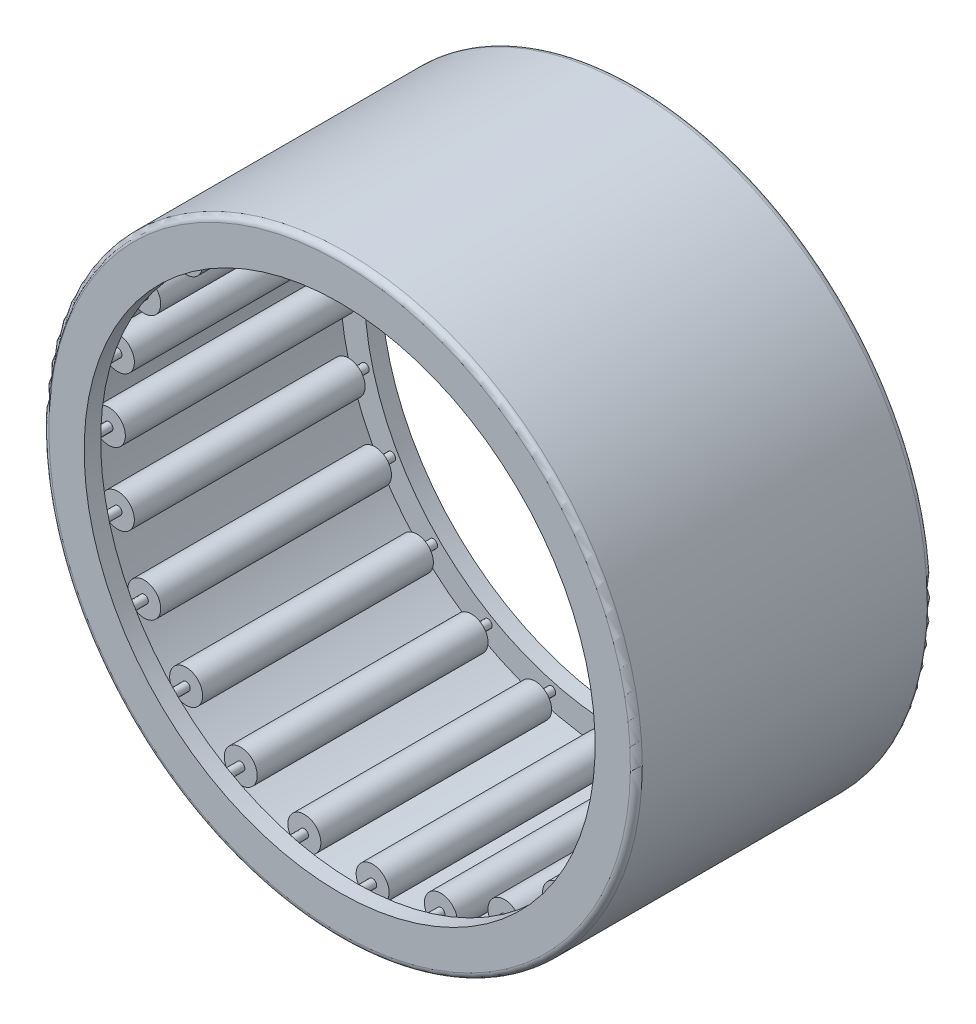
SolidWorks part; units mm, degrees
ref_plane "Front Plane" through (0, 0, 0) normal (0, 0, 1) x (1, 0, 0)
ref_plane "Top Plane" through (0, 0, 0) normal (0, 1, 0) x (1, 0, 0)
ref_plane "Right Plane" through (0, 0, 0) normal (1, 0, 0) x (0, 0, -1)
sketch "Sketch1" plane through (0, 0, 0) normal (1, 0, 0) x (0, 0, -1)
  line L0 (-9.525, 0) -> (9.525, 0) construction
  line L1 (0, 0) -> (0, 19.05) construction
  line L2 (-9.525, 0) -> (-9.525, 19.05) construction
  line L3 (-9.525, 19.05) -> (9.525, 19.05)
  line L4 (9.525, 19.05) -> (9.525, 0) construction
  line L5 (9.525, 0) -> (8.4667, 0) construction
  line L6 (8.4667, 0) -> (8.4667, 17.9917) construction
  line L7 (8.4667, 17.9917) -> (-8.4667, 17.9917)
  line L8 (-8.4667, 17.9917) -> (-8.4667, 0) construction
  line L9 (-8.4667, 0) -> (-9.525, 0) construction
  line L10 (-9.525, 19.05) -> (-9.525, 16.4042)
  line L11 (-9.525, 16.4042) -> (-8.4667, 16.4042)
  line L12 (-8.4667, 16.4042) -> (-8.4667, 17.9917)
  line L13 (8.4667, 19.05) -> (8.4667, 17.9917) construction
  line L14 (8.4667, 17.9917) -> (8.4667, 16.4042)
  line L15 (8.4667, 16.4042) -> (9.525, 16.4042)
  line L16 (9.525, 16.4042) -> (9.525, 19.05)
  line L17 (8.4667, 17.9917) -> (8.4667, 16.9333) construction
  line L18 (8.4667, 16.9333) -> (8.4667, 15.875) construction
  line L19 (8.4667, -17.9917) -> (8.4667, -16.9333) construction
  line L20 (8.4667, -19.05) -> (8.4667, -17.9917) construction
  line L21 (9.525, -16.4042) -> (9.525, -19.05) construction
  line L22 (8.4667, -16.4042) -> (9.525, -16.4042) construction
  line L23 (8.4667, -17.9917) -> (8.4667, -16.4042) construction
  line L24 (-8.4667, -16.4042) -> (-8.4667, -17.9917) construction
  line L25 (-9.525, -16.4042) -> (-8.4667, -16.4042) construction
  line L26 (-9.525, -19.05) -> (-9.525, -16.4042) construction
  line L27 (8.4667, -17.9917) -> (-8.4667, -17.9917) construction
  line L28 (-9.525, -19.05) -> (9.525, -19.05) construction
  point P5 (0, 15.875)
  dimension "Width" = 19.05
  dimension "OD" = 38.1
  dimension "Shaft Dia" = 31.75
revolve "Revolve1" add sketch "Sketch1" angle 360 about L0
sketch "Sketch2" plane through (0, 0, 0) normal (1, 0, 0) x (0, 0, -1)
  line L0 (8.4667, 17.9917) -> (-8.4667, 17.9917) construction
  line L1 (-7.4083, 16.9333) -> (7.4083, 16.9333) construction
  line L2 (-7.4083, 16.9333) -> (-7.4083, 17.9917) construction
  line L3 (-7.4083, 17.9917) -> (7.4083, 17.9917)
  line L4 (7.4083, 16.9333) -> (7.4083, 17.9917) construction
  line L5 (8.4667, 16.4042) -> (9.525, 16.4042) construction
  line L6 (-8.4667, 16.9333) -> (-7.4083, 16.9333) construction
  line L7 (7.4083, 16.9333) -> (8.4667, 16.9333) construction
  line L8 (-9.525, 16.4042) -> (-8.4667, 16.4042) construction
  line L9 (-7.4083, 17.1979) -> (-7.4083, 16.6688) construction
  line L10 (-8.4667, 16.9333) -> (-8.4667, 16.4042) construction
  line L11 (-7.4083, 17.9917) -> (-7.4083, 17.1979)
  line L12 (7.4083, 17.9917) -> (7.4083, 17.1979)
  line L13 (7.4083, 17.1979) -> (-7.4083, 17.1979)
  line L14 (0, 17.9917) -> (0, 15.875) construction
  line L15 (-8.4667, 16.4042) -> (-8.4667, 17.9917) construction
  line L16 (-7.4083, 16.6688) -> (-8.4667, 16.6688) construction
  line L17 (0, 0) -> (9.525, 0) construction
  line L18 (-7.4083, -16.6688) -> (-8.4667, -16.6688) construction
  line L19 (0, -17.9917) -> (0, -15.875) construction
  line L20 (-8.4667, -16.9333) -> (-8.4667, -16.4042) construction
  line L21 (-7.4083, -17.1979) -> (-7.4083, -16.6688) construction
  line L22 (7.4083, -16.9333) -> (8.4667, -16.9333) construction
  line L23 (-8.4667, -16.9333) -> (-7.4083, -16.9333) construction
  line L24 (7.4083, -16.9333) -> (7.4083, -17.9917) construction
  line L25 (-7.4083, -16.9333) -> (-7.4083, -17.9917) construction
  line L26 (-7.4083, -16.9333) -> (7.4083, -16.9333) construction
  line L27 (7.4083, -17.1979) -> (-7.4083, -17.1979) construction
  line L28 (7.4083, -17.9917) -> (7.4083, -17.1979) construction
  line L29 (-7.4083, -17.9917) -> (-7.4083, -17.1979) construction
  line L30 (-7.4083, -17.9917) -> (7.4083, -17.9917) construction
  line L31 (9.525, -19.05) -> (9.525, 19.05) construction
  point P16 (0, 16.9333)
revolve "Revolve2" add sketch "Sketch2" angle 360 about L1
sketch "Sketch3" plane through (0, 0, 0) normal (1, 0, 0) x (0, 0, -1)
  line L0 (8.4667, 17.9917) -> (8.4667, 16.4042) construction
  line L1 (-8.4667, 16.9333) -> (8.4667, 16.9333)
  line L2 (-8.4667, 16.9333) -> (-8.4667, 17.1979)
  line L3 (-8.4667, 17.1979) -> (8.4667, 17.1979)
  line L4 (8.4667, 16.9333) -> (8.4667, 17.1979)
  line L5 (0, 0) -> (9.525, 0) construction
  line L6 (9.525, -19.05) -> (9.525, 19.05) construction
  line L7 (8.4667, -16.9333) -> (8.4667, -17.1979) construction
  line L8 (-8.4667, -17.1979) -> (8.4667, -17.1979) construction
  line L9 (-8.4667, -16.9333) -> (-8.4667, -17.1979) construction
  line L10 (-8.4667, -16.9333) -> (8.4667, -16.9333) construction
revolve "Revolve3" add sketch "Sketch3" angle 360 about L1
ref_axis "Axis1" through (0, 0, -9.525) along (0, 0, 1)
pattern_circular "CirPattern1" count 24 over 360 about axis through (0, 0, -9.525) along (0, 0, 1) of bodies 166 167
fillet "Fillet1" radius 0.381 2 edges at (0, -19.05, -9.525) (0, -19.05, 9.525)
sketch "Sketch4" plane through (0, 0, 0) normal (1, 0, 0) x (0, 0, -1)
  line L1 (9.144, 15.875) -> (7.4083, 15.875)
  line L2 (9.144, 15.875) -> (9.144, 16.4042)
  line L3 (9.144, 16.4042) -> (7.4083, 16.4042)
  line L4 (7.4083, 15.875) -> (7.4083, 16.4042)
  line L5 (-9.525, 16.4042) -> (-8.4667, 16.4042) construction
  line L6 (9.144, -19.05) -> (9.144, 19.05) construction
  line L7 (7.4083, 17.9917) -> (7.4083, 17.1979) construction
revolve "Revolve4" [suppressed] add sketch "Sketch4" angle 360 about L0
sketch "Sketch5" plane through (0, 0, 0) normal (1, 0, 0) x (0, 0, -1)
  line L0 (-9.144, 19.05) -> (-9.144, -19.05) construction
  line L1 (-7.4083, 15.875) -> (-9.144, 15.875)
  line L2 (-7.4083, 15.875) -> (-7.4083, 16.4042)
  line L3 (-7.4083, 16.4042) -> (-9.144, 16.4042)
  line L4 (-9.144, 15.875) -> (-9.144, 16.4042)
  line L6 (-7.4083, 17.9917) -> (-7.4083, 17.1979) construction
  line L7 (-9.525, 16.4042) -> (-8.4667, 16.4042) construction
revolve "Revolve5" [suppressed] add sketch "Sketch5" angle 360 about L0
equation "\"Angle@CirPattern1\" = 360/\"Rollers@CirPattern1\""
equation "\"Rollers@CirPattern1\" = \"OD@Sketch1\"*16"
equation "\"D1@Fillet1\" = \"OD@Sketch1\"*.01"
